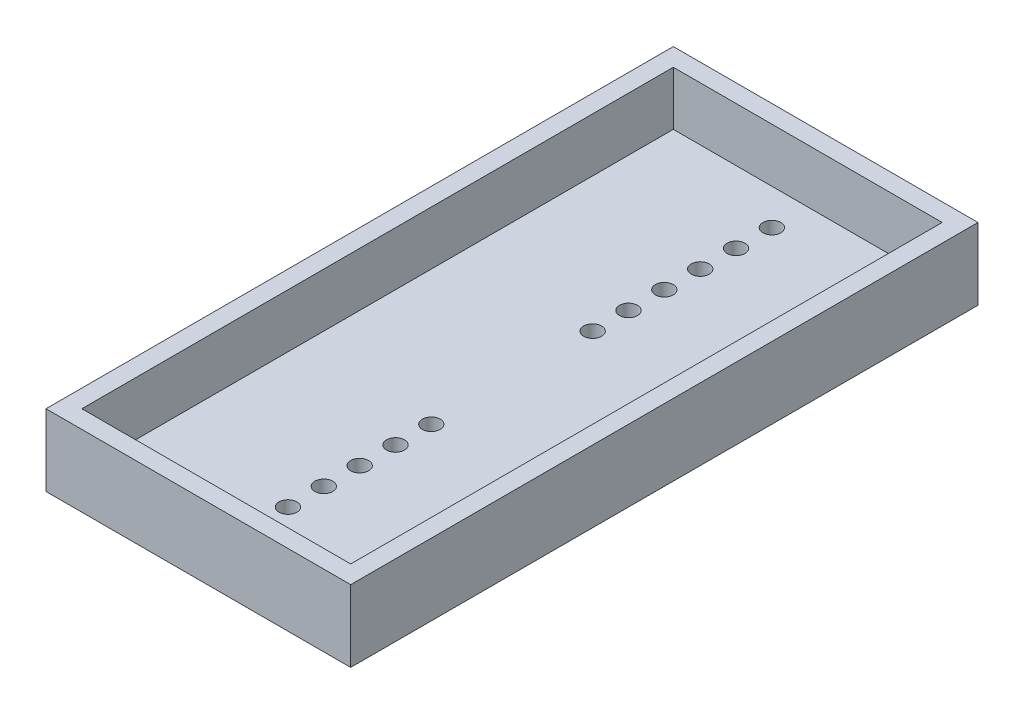
SolidWorks part; units mm, degrees
ref_plane "前视基准面" through (0, 0, 0) normal (0, 0, 1) x (1, 0, 0)
ref_plane "上视基准面" through (0, 0, 0) normal (0, 1, 0) x (1, 0, 0)
ref_plane "右视基准面" through (0, 0, 0) normal (1, 0, 0) x (0, 0, -1)
sketch "草图1" plane through (0, 0, 0) normal (0, 1, 0) x (1, 0, 0)
  line L0 (-8.5, 17.5) -> (8.5, 17.5)
  line L1 (-7.5, 16.5) -> (7.5, 16.5)
  line L2 (-7.5, 16.5) -> (-7.5, -16.5)
  line L3 (-7.5, -16.5) -> (7.5, -16.5)
  line L4 (7.5, 16.5) -> (7.5, -16.5)
  line L5 (-7.5, 16.5) -> (7.5, -16.5) construction
  line L6 (-7.5, -16.5) -> (7.5, 16.5) construction
  line L7 (8.5, 17.5) -> (8.5, -17.5)
  line L8 (-8.5, -17.5) -> (8.5, -17.5)
  line L9 (-8.5, 17.5) -> (-8.5, -17.5)
  point P0 (0, 0)
  dimension "D1" = 33
  dimension "D2" = 15
  dimension "D3" = 1
extrude "凸台-拉伸1" add sketch "草图1" along normal blind 4
extrude "凸台-拉伸2" add sketch "草图1<2>" along normal blind 1 contours L4 L1 L2 L3 region at (0, 0, 0)
sketch "草图1<2>" plane through (0, 0, 0) normal (0, 1, 0) x (1, 0, 0) same geometry as "草图1"
sketch "草图2" plane through (0, 0, 0) normal (0, -1, 0) x (1, 0, 0)
  line L0 (0, 14.5) -> (0, -14.5) construction
  line L3 (-4.6922, 0) -> (5.1332, 0) construction
  circle A0 centre (0, 14.5) radius 0.5
  circle A1 centre (0, 12.5) radius 0.5
  circle A2 centre (0, 10.5) radius 0.5
  circle A3 centre (0, 8.5) radius 0.5
  circle A4 centre (0, 6.5) radius 0.5
  circle A5 centre (0, 4.5) radius 0.5
  circle A6 centre (0, -4.5) radius 0.5
  circle A7 centre (0, -6.5) radius 0.5
  circle A8 centre (0, -8.5) radius 0.5
  circle A9 centre (0, -10.5) radius 0.5
  circle A10 centre (0, -12.5) radius 0.5
  circle A11 centre (0, -14.5) radius 0.5
  dimension "D1" = 1
  dimension "D2" = 29
  dimension "D3" = 6
extrude "切除-拉伸1" cut sketch "草图2" against normal through all
